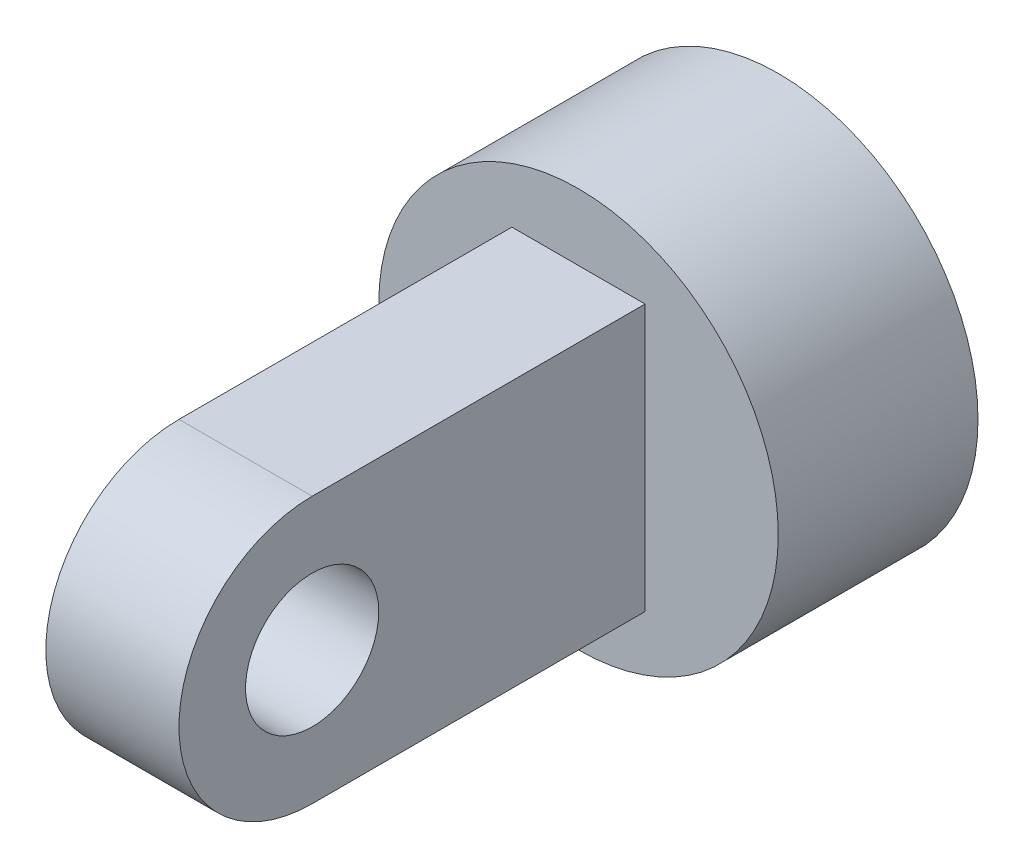
SolidWorks part; units mm, degrees
ref_plane "Front Plane" through (0, 0, 0) normal (0, 0, 1) x (1, 0, 0)
ref_plane "Top Plane" through (0, 0, 0) normal (0, 1, 0) x (1, 0, 0)
ref_plane "Right Plane" through (0, 0, 0) normal (1, 0, 0) x (0, 0, -1)
sketch "Sketch1" plane through (0, 0, 0) normal (1, 0, 0) x (0, 0, -1)
  circle A0 centre (0, 0) radius 12.7
  dimension "D1" = 25.4
extrude "Extrude-Thin1" add sketch "Sketch1" along normal blind 12.7 thin contours A0 thin type one direction reverse wall 6.35
ref_axis "Axis1" through (12.7, 0, 0) along (-1, 0, 0)
ref_plane "Plane1" through (6.35, 0, 0) normal (-1, 0, 0) x (0, 0, 1)
sketch "Sketch2" plane through (12.7, 0, 0) normal (1, 0, 0) x (0, 0, -1)
  line L0 (0, 12.7) -> (31.75, 12.7)
  line L1 (31.75, 12.7) -> (31.75, -12.7)
  line L2 (31.75, -12.7) -> (0, -12.7)
  circle A0 centre (0, 0) radius 12.7 construction
  arc A1 (0, -12.7) -> (0, 12.7) centre (0, 0) ccw
  dimension "D1" = 31.75
extrude "Boss-Extrude1" add sketch "Sketch2" against normal up to surface (12.7 mm away) up to face at (0, 0, -12.7)
sketch "Sketch3" plane through (0, 0, -31.75) normal (0, 0, -1) x (-1, 0, 0)
  line L0 (-6.35, -13.97) -> (-6.35, 13.97) construction
  line L1 (-12.7, 0) -> (0, 0) construction
  circle A0 centre (-6.35, 0) radius 19.05
  dimension "D1" = 38.1
extrude "Boss-Extrude2" add sketch "Sketch3" along normal blind 19.05
sketch "Sketch4" plane through (0, 0, -50.8) normal (0, 0, -1) x (-1, 0, 0)
  line L0 (-6.35, -13.97) -> (-6.35, 13.97) construction
  line L1 (-12.7, 0) -> (0, 0) construction
  circle A0 centre (-6.35, 0) radius 12.7
  circle A1 centre (-6.35, 0) radius 19.05 construction
  dimension "D1" = 25.4
extrude "Cut-Extrude1" cut sketch "Sketch4" against normal blind 6.35
